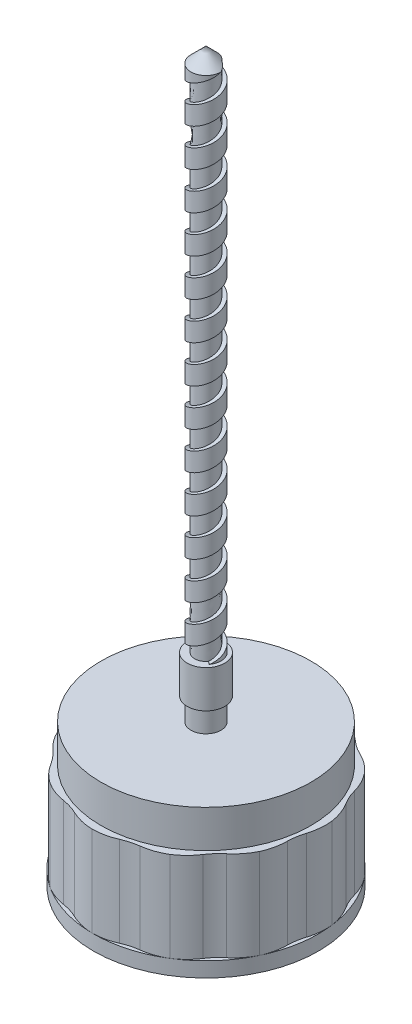
SolidWorks part; units mm, degrees
ref_plane "Front Plane" through (0, 0, 0) normal (0, 0, 1) x (1, 0, 0)
ref_plane "Top Plane" through (0, 0, 0) normal (0, 1, 0) x (1, 0, 0)
ref_plane "Right Plane" through (0, 0, 0) normal (1, 0, 0) x (0, 0, -1)
sketch "Sketch1" plane through (0, 0, 0) normal (0, 1, 0) x (1, 0, 0)
  circle A0 centre (0, 0) radius 15
  dimension "D1" = 30
extrude "Boss-Extrude1" add sketch "Sketch1" along normal blind 14
sketch "Sketch4" plane through (0, 14, 0) normal (0, 1, 0) x (1, 0, 0)
  arc A0 (12.9119, 6.8671) -> (13.8017, 4.8362) centre (20.151, 8.8282) ccw
  arc A1 (12.9119, 6.8671) -> (11.3458, 9.8119) centre (5.6729, 4.906) ccw
  arc A2 (14.9047, 1.6885) -> (11.3458, 9.8119) centre (0, 0) ccw
  arc A3 (14.9047, 1.6885) -> (13.8017, 4.8362) centre (7.4523, 0.8442) ccw
  dimension "D1" = 15
  dimension "D4" = 15
  dimension "D5" = 15
  dimension "D2" = 22
  dimension "D3" = 7.5
extrude "Cut-Extrude1" cut sketch "Sketch4" against normal blind 12
pattern_circular "CirPattern1" count 11 over 360 about axis through (0, 0, 0) along (0, 1, 0) of "Cut-Extrude1"
sketch "Sketch5" plane through (0, 14, 0) normal (0, 1, 0) x (1, 0, 0)
  circle A0 centre (0, 0) radius 14
  dimension "D1" = 28
extrude "Boss-Extrude2" add sketch "Sketch5" along normal blind 5
sketch "Sketch6" plane through (0, 19, 0) normal (0, 1, 0) x (1, 0, 0)
  circle A0 centre (0, 0) radius 2
  dimension "D1" = 4
extrude "Boss-Extrude3" add sketch "Sketch6" along normal blind 3
sketch "Sketch7" plane through (0, 22, 0) normal (0, 1, 0) x (1, 0, 0)
  circle A0 centre (0, 0) radius 2.5
  dimension "D1" = 5
extrude "Boss-Extrude4" add sketch "Sketch7" along normal blind 5
sketch "Sketch9" plane through (0, 27, 0) normal (0, 1, 0) x (1, 0, 0)
  circle A0 centre (0, 0) radius 2
  dimension "D1" = 4
extrude "Boss-Extrude5" add sketch "Sketch9" along normal blind 70
sketch "Sketch10" plane through (0, 97, 0) normal (0, 1, 0) x (1, 0, 0)
  circle A1 centre (0, 0) radius 2
curve "Helix/Spiral1" pitch 5 height 70 turns 14
chamfer "Chamfer1" distance 2 angle 45 1 edges at (0, 97, 2)
sketch "Sketch11" plane through (0, 0, 0) normal (0, 0, 1) x (1, 0, 0)
  line L1 (-2, 95) -> (-1.5, 95)
  line L2 (-2, 95) -> (-2, 97.5)
  line L3 (-2, 97.5) -> (-1.5, 97.5)
  line L4 (-1.5, 95) -> (-1.5, 97.5)
  dimension "D1" = 0.5
  dimension "D2" = 2.5
sweep "Cut-Sweep1" cut profiles "Sketch11" path "Helix/Spiral1" align with end faces yes
sketch "Sketch12" plane through (0, 0, 0) normal (0, -1, 0) x (1, 0, 0)
  circle A0 centre (0, 0) radius 14
  dimension "D1" = 28
extrude "Cut-Extrude2" cut sketch "Sketch12" against normal blind 13
scale "Scale1" scale about origin uniform scaling yes scale factor 0.655
equation "\"D2@Sketch4\"=14.5+(\"D1@Sketch4\"/2)"
